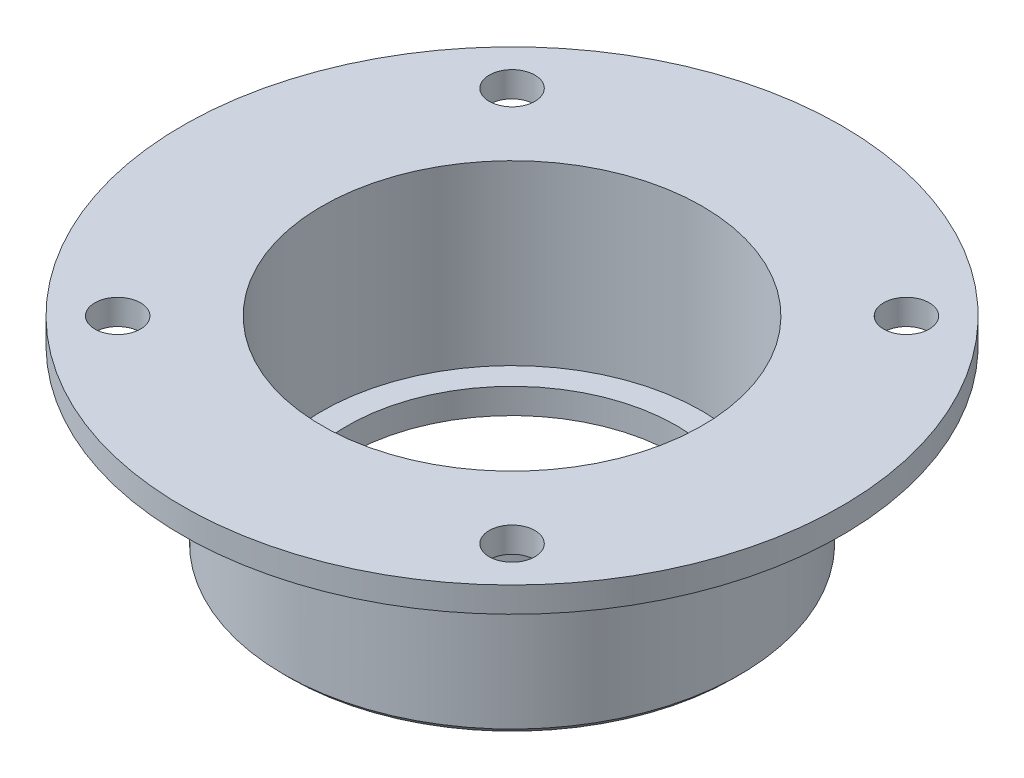
SolidWorks part; units mm, degrees
ref_plane "Спереди" through (0, 0, 0) normal (0, 0, 1) x (1, 0, 0)
ref_plane "Сверху" through (0, 0, 0) normal (0, 1, 0) x (1, 0, 0)
ref_plane "Справа" through (0, 0, 0) normal (1, 0, 0) x (0, 0, -1)
sketch "Эскиз1" plane through (0, 0, 0) normal (0, 0, 1) x (1, 0, 0)
  line L0 (0, 0) -> (0, 8.0722) construction
  line L1 (-15, 2) -> (-15, 16)
  line L2 (-15, 16) -> (-26, 16)
  line L3 (-26, 16) -> (-26, 14)
  line L4 (-26, 14) -> (-18, 14)
  line L5 (-18, 14) -> (-18, 0)
  line L6 (-18, 0) -> (-13, 0)
  line L7 (-13, 0) -> (-13, 2)
  line L8 (-13, 2) -> (-15, 2)
  line L12 (-15, 15.4) -> (15, 15.4) construction
  line L13 (-15, 15.4) -> (15, 15.4) construction
  line L14 (14.4, 16) -> (-14.4, 16) construction
  dimension "D1" = 2
  dimension "D2" = 3
  dimension "D3" = 8
  dimension "D4" = 30
  dimension "D5" = 30
  dimension "D6" = 2
  dimension "D7" = 2
revolve "Повернуть1" add sketch "Эскиз1" angle 360 about L0
chamfer "Фаска1" distance 0.5 angle 45 1 edges at (0, 0, -18)
hole_wizard "Отверстие с зазором M31" positions "Эскиз2" profile "Эскиз3" hole size "M3" standard "DIN" end condition up to next
sketch "Эскиз2" plane through (0, 16, 0) normal (0, 1, 0) x (1, 0, 0)
  line L1 (12.7279, -12.7279) -> (18.3848, -18.3848) construction
  line L3 (0, 0) -> (50000, 0) construction
  circle A1 centre (0, 0) radius 26 construction
  circle A2 centre (0, 0) radius 18 construction
  circle A3 centre (0, 0) radius 26 construction
  circle A4 centre (0, 0) radius 18 construction
  circle A5 centre (0, 0) radius 26 construction
  point P39 (15.5563, -15.5563)
  dimension "D1" = 45
sketch "Эскиз3" plane through (15.5563, 16, 15.5563) normal (1, 0, 0) x (0, 0, 1)
  line L0 (0, 0) -> (0, 2)
  line L1 (0, 2) -> (1.8, 2)
  line L2 (1.8, 2) -> (1.8, 0)
  line L5 (1.8, 0) -> (0, 0)
  line L11 (0, -6.35) -> (0, 107.95) construction
  dimension "Диаметр сквозного отверстия" = 3.6
  dimension "Глубина сквозного отверстия" = 2
pattern_circular "Круговой массив1" count 4 over 360 about axis through (0, 0, 0) along (0, -1, 0) of "Отверстие с зазором M31" reverse direction yes
equation "\"D5@Эскиз1\"=\"D4@Эскиз1\""
